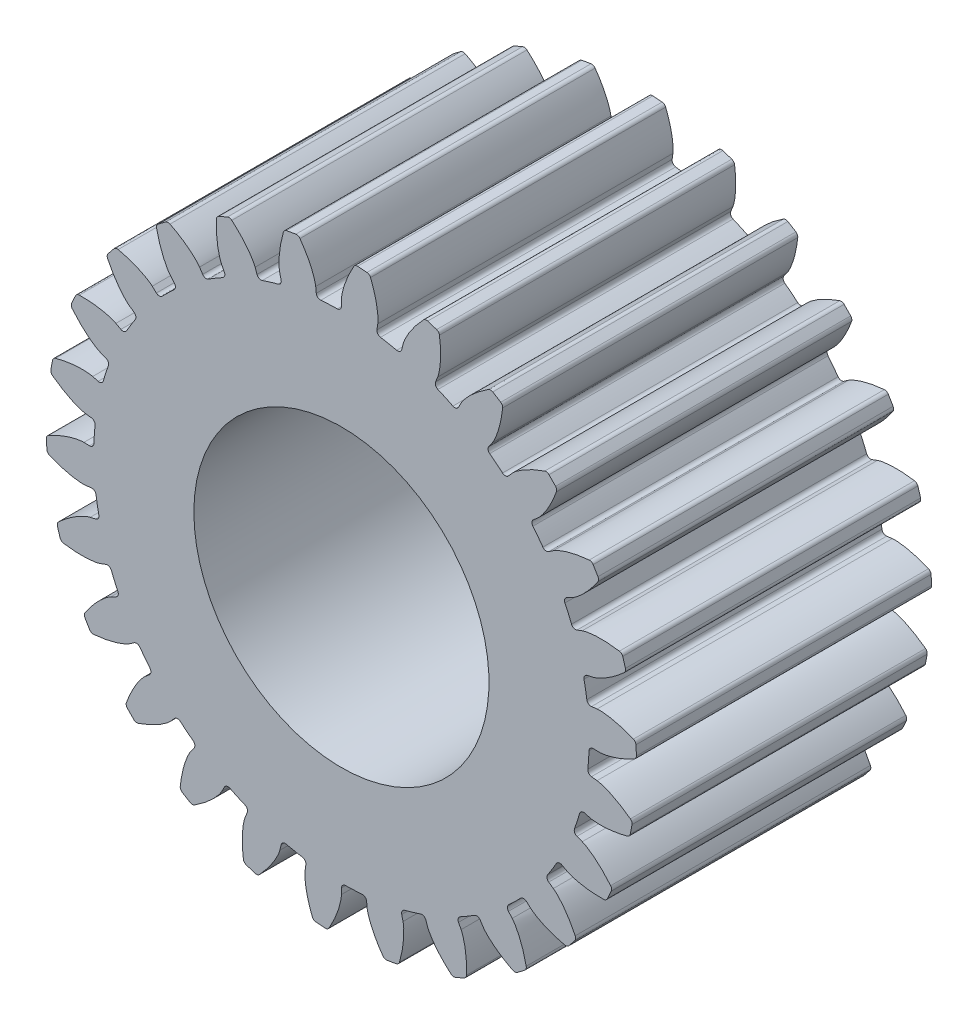
SolidWorks part; units mm, degrees
ref_plane "Front Plane" through (0, 0, 0) normal (0, 0, 1) x (1, 0, 0)
ref_plane "Top Plane" through (0, 0, 0) normal (0, 1, 0) x (1, 0, 0)
ref_plane "Right Plane" through (0, 0, 0) normal (1, 0, 0) x (0, 0, -1)
sketch "Involute Geometry" plane through (0, 0, 0) normal (0, 0, 1) x (1, 0, 0)
  line L0 (0, 12.216) -> (0, 0) construction
  line L1 (0, 0) -> (0.9904, 13.9649) construction
  line L2 (1.724, 12.0937) -> (0, 0) construction
  line L3 (0.175, 12.9988) -> (0, 0) construction
  line L4 (0, 0) -> (1.6612, 12.8934) construction
  circle A1 centre (0, 0) radius 12.216 construction
  circle A2 centre (0, 0) radius 13 construction
  circle A3 centre (0, 0) radius 14 construction
  circle A4 centre (0, 0) radius 11.75 construction
  arc A5 (0.6454, 13.9851) -> (1.3347, 13.9362) centre (0, 0) cw
  arc A6 (0.175, 12.9988) -> (1.6612, 12.8934) centre (0, 0) cw construction
  spline S0 degree 4 poles (0, 12.216) (0, 12.2259) (0.0007, 12.2537) (0.0046, 12.3061) (0.0149, 12.3914) (0.0336, 12.4994) (0.064, 12.638) (0.108, 12.7997) (0.1647, 12.9755) (0.2354, 13.1642) (0.3138, 13.35) (0.3992, 13.5328) (0.4907, 13.7124) (0.6089, 13.9268) (0.7611, 14.1794) (0.9535, 14.4672) (1.1888, 14.7846) (1.4461, 15.0973) (1.7136, 15.3959) (1.9994, 15.6864) (2.287, 15.9594) (2.6008, 16.2305) (2.8982, 16.4744) (3.2472, 16.733) (3.5335, 16.9374) (3.9271, 17.1908) (4.1642, 17.3355) (4.4469, 17.4991) (4.5752, 17.5686) (4.654, 17.6115) knots 0 0 0 0 0 0.005377 0.015084 0.028532 0.04661 0.064855 0.092111 0.119476 0.146842 0.174209 0.201575 0.228941 0.256307 0.307035 0.361767 0.4165 0.471232 0.525964 0.580697 0.635429 0.690161 0.744894 0.799626 0.854358 0.909091 0.954545 1 1 1 1 1 construction
  spline S1 degree 4 poles (0, 12.216) (0, 12.2259) (0.0007, 12.2537) (0.0046, 12.3061) (0.0149, 12.3914) (0.0336, 12.4994) (0.064, 12.638) (0.108, 12.7997) (0.1647, 12.9755) (0.2354, 13.1642) (0.3138, 13.35) (0.3992, 13.5328) (0.4907, 13.7124) (0.6089, 13.9268) (0.7611, 14.1794) (0.9535, 14.4672) (1.1888, 14.7846) (1.4461, 15.0973) (1.7136, 15.3959) (1.9994, 15.6864) (2.287, 15.9594) (2.6008, 16.2305) (2.8982, 16.4744) (3.2472, 16.733) (3.5335, 16.9374) (3.8418, 17.1359) (3.9936, 17.2306) (4.0719, 17.2782) knots 0 0 0 0 0 0.005377 0.015084 0.028532 0.04661 0.064855 0.092111 0.119476 0.146842 0.174209 0.201575 0.228941 0.256307 0.307035 0.361767 0.4165 0.471232 0.525964 0.580697 0.635429 0.690161 0.744894 0.799626 0.854358 0.909091 0.909091 0.909091 0.909091 0.909091
  spline S3 degree 4 poles (1.724, 12.0937) (1.7254, 12.1035) (1.7287, 12.1311) (1.7321, 12.1836) (1.734, 12.2695) (1.7308, 12.379) (1.7202, 12.5206) (1.6995, 12.6869) (1.6681, 12.8689) (1.6248, 13.0657) (1.5734, 13.2607) (1.5147, 13.4537) (1.4495, 13.6444) (1.3626, 13.8734) (1.2477, 14.1449) (1.0977, 14.457) (0.9096, 14.8044) (0.699, 15.1503) (0.4764, 15.4836) (0.2344, 15.8116) (-0.0118, 16.1224) (-0.2842, 16.4351) (-0.5442, 16.7185) (-0.8532, 17.0238) (-1.1078, 17.2666) (-1.4617, 17.573) (-1.676, 17.7497) (-1.9328, 17.9515) (-2.05, 18.0384) (-2.122, 18.092) knots 0 0 0 0 0 0.005377 0.015084 0.028532 0.04661 0.064855 0.092111 0.119476 0.146842 0.174209 0.201575 0.228941 0.256307 0.307035 0.361767 0.4165 0.471232 0.525964 0.580697 0.635429 0.690161 0.744894 0.799626 0.854358 0.909091 0.954545 1 1 1 1 1 construction
  spline S4 degree 4 poles (1.724, 12.0937) (1.7254, 12.1035) (1.7287, 12.1311) (1.7321, 12.1836) (1.734, 12.2695) (1.7308, 12.379) (1.7202, 12.5206) (1.6995, 12.6869) (1.6681, 12.8689) (1.6248, 13.0657) (1.5734, 13.2607) (1.5147, 13.4537) (1.4495, 13.6444) (1.3626, 13.8734) (1.2477, 14.1449) (1.0977, 14.457) (0.9096, 14.8044) (0.699, 15.1503) (0.4764, 15.4836) (0.2344, 15.8116) (-0.0118, 16.1224) (-0.2842, 16.4351) (-0.5442, 16.7185) (-0.8532, 17.0238) (-1.1078, 17.2666) (-1.385, 17.5066) (-1.5219, 17.6217) (-1.5927, 17.6799) knots 0 0 0 0 0 0.005377 0.015084 0.028532 0.04661 0.064855 0.092111 0.119476 0.146842 0.174209 0.201575 0.228941 0.256307 0.307035 0.361767 0.4165 0.471232 0.525964 0.580697 0.635429 0.690161 0.744894 0.799626 0.854358 0.909091 0.909091 0.909091 0.909091 0.909091
  dimension "D5" = 6.57
sketch "Sketch2" plane through (0, 0, 0) normal (0, 0, 1) x (1, 0, 0)
  circle A0 centre (0, 0) radius 11.75 construction
  circle A1 centre (0, 0) radius 11.75
extrude "Boss-Extrude1" add sketch "Sketch2" along normal mid plane 14
sketch "Sketch3" plane through (0, 0, 0) normal (0, 0, 1) x (1, 0, 0)
  line L0 (0, 12.216) -> (0, 0) construction
  line L1 (1.724, 12.0937) -> (0, 0) construction
  line L2 (0, 12.216) -> (0, 11.75)
  line L4 (1.724, 12.0937) -> (1.6583, 11.6324)
  circle A1 centre (0, 0) radius 11.75 construction
  arc A3 (0, 11.75) -> (1.6583, 11.6324) centre (0, 0) cw
  arc A4 (1.3347, 13.9362) -> (0.6454, 13.9851) centre (0, 0) ccw construction
  arc A5 (1.3347, 13.9362) -> (0.6454, 13.9851) centre (0, 0) ccw
  spline S0 degree 4 poles (999.8581, 25.2356) (18.0155, 10.2173) (0.3577, 10.7107) (-0.0848, 11.5636) (0.0149, 12.3914) (0.0336, 12.4994) (0.064, 12.638) (0.108, 12.7997) (0.1647, 12.9755) (0.2354, 13.1642) (0.3138, 13.35) (0.3992, 13.5328) (0.4907, 13.7124) (0.6089, 13.9268) (0.7611, 14.1794) (0.9535, 14.4672) (1.1888, 14.7846) (1.4461, 15.0973) (1.7136, 15.3959) (1.9994, 15.6864) (2.287, 15.9594) (2.6008, 16.2305) (2.8982, 16.4744) (3.2472, 16.733) (4.4419, 17.5861) (8.1221, 19.6216) (-23.9178, -0.2396) (859.2438, 535.5339) knots -0.405932 -0.405932 -0.405932 -0.405932 -0.405932 0.005377 0.015084 0.028532 0.04661 0.064855 0.092111 0.119476 0.146842 0.174209 0.201575 0.228941 0.256307 0.307035 0.361767 0.4165 0.471232 0.525964 0.580697 0.635429 0.690161 0.744894 0.799626 0.854358 1.603617 1.603617 1.603617 1.603617 1.603617 only from (0, 12.216) to (3.8711, 11.595) construction
  spline S1 degree 4 poles (0, 12.216) (0, 12.2259) (0.0007, 12.2537) (0.0046, 12.3061) (0.0149, 12.3914) (0.0336, 12.4994) (0.064, 12.638) (0.108, 12.7997) (0.1647, 12.9755) (0.2354, 13.1642) (0.3138, 13.35) (0.3992, 13.5328) (0.4919, 13.7149) (0.5664, 13.8498) (0.6183, 13.9394) (0.6454, 13.9851) knots 0 0 0 0 0 0.005377 0.015084 0.028532 0.04661 0.064855 0.092111 0.119476 0.146842 0.174209 0.201575 0.228941 0.257808 0.257808 0.257808 0.257808 0.257808
  spline S3 degree 4 poles (-986.2895, 166.0908) (-16.3932, 12.6575) (1.1575, 10.654) (1.7159, 11.4359) (1.734, 12.2695) (1.7308, 12.379) (1.7202, 12.5206) (1.6995, 12.6869) (1.6681, 12.8689) (1.6248, 13.0657) (1.5734, 13.2607) (1.5147, 13.4537) (1.4495, 13.6444) (1.3626, 13.8734) (1.2477, 14.1449) (1.0977, 14.457) (0.9096, 14.8044) (0.699, 15.1503) (0.4764, 15.4836) (0.2344, 15.8116) (-0.0118, 16.1224) (-0.2842, 16.4351) (-0.5442, 16.7185) (-0.8532, 17.0238) (-1.9155, 18.037) (-5.2716, 20.5715) (23.6446, -3.6127) (-775.0652, 651.4371) knots -0.405932 -0.405932 -0.405932 -0.405932 -0.405932 0.005377 0.015084 0.028532 0.04661 0.064855 0.092111 0.119476 0.146842 0.174209 0.201575 0.228941 0.256307 0.307035 0.361767 0.4165 0.471232 0.525964 0.580697 0.635429 0.690161 0.744894 0.799626 0.854358 1.603617 1.603617 1.603617 1.603617 1.603617 only from (1.724, 12.0937) to (-1.5927, 17.6799) construction
  spline S4 degree 4 poles (1.724, 12.0937) (1.7254, 12.1035) (1.7287, 12.1311) (1.7321, 12.1836) (1.734, 12.2695) (1.7308, 12.379) (1.7202, 12.5206) (1.6995, 12.6869) (1.6681, 12.8689) (1.6248, 13.0657) (1.5734, 13.2607) (1.5147, 13.4537) (1.4486, 13.647) (1.3938, 13.7911) (1.3551, 13.8871) (1.3347, 13.9362) knots 0 0 0 0 0 0.005377 0.015084 0.028532 0.04661 0.064855 0.092111 0.119476 0.146842 0.174209 0.201575 0.228941 0.257808 0.257808 0.257808 0.257808 0.257808
extrude "Boss-Extrude2" add sketch "Sketch3" along normal through all and the other way through all
fillet "Fillet2" [suppressed] radius 0.381
pattern_circular "CirPattern1" count 26 over 360 about axis through (0, 0, 7) along (0, 0, -1) of "Boss-Extrude2", "Fillet2"
ref_axis "Axis1" through (0, 0, 7) along (0, 0, -1)
sketch "Sketch4" plane through (0, 0, -7) normal (0, 0, -1) x (-1, 0, 0)
  circle A1 centre (0, 0) radius 7
  dimension "D1" = 14
extrude "Cut-Extrude1" cut sketch "Sketch4" against normal through all
fillet "Fillet3" radius 0.2 104 edges at (-8.6313, 7.9727, 0) (-9.6701, 6.6748, 0) (-10.9864, 4.1666, 0) (-11.3477, 3.0483, 0) (-11.6643, 1.4163, 0) (-11.7475, 0.244, 0) (-11.6643, -1.4163, 0) (-11.4645, -2.5744, 0) (-10.9864, -4.1666, 0) (-10.5153, -5.2432, 0) (-9.6701, -6.6748, 0) (-8.9549, -7.6074, 0) (-7.7917, -8.795, 0) (-6.8742, -9.5293, 0) (-5.4605, -10.4041, 0) (-4.3939, -10.8975, 0) (-2.812, -11.4086, 0) (-1.6583, -11.6324, 0) (0, -11.75, 0) (1.1737, -11.6912, 0) (2.812, -11.4086, 0) (3.9375, -11.0706, 0) (5.4605, -10.4041, 0) (6.4725, -9.8066, 0) (7.7917, -8.795, 0) (8.6313, -7.9727, 0) (9.6701, -6.6748, 0) (10.2885, -5.6754, 0) (10.9864, -4.1666, 0) (11.3477, -3.0483, 0) (11.6643, -1.4163, 0) (11.7475, -0.244, 0) (11.6643, 1.4163, 0) (11.4645, 2.5744, 0) (10.9864, 4.1666, 0) (10.5153, 5.2432, 0) (9.6701, 6.6748, 0) (8.9549, 7.6074, 0) (7.7917, 8.795, 0) (6.8742, 9.5293, 0) (5.4605, 10.4041, 0) (4.3939, 10.8975, 0) (2.812, 11.4086, 0) (1.6583, 11.6324, 0) (0, 11.75, 0) (-10.2885, 5.6754, 0) (-1.1737, 11.6912, 0) (-2.812, 11.4086, 0) (-3.9375, 11.0706, 0) (-5.4605, 10.4041, 0) (-6.4725, 9.8066, 0) (-7.7917, 8.795, 0) (1.3347, 13.9362, 0) (3.9735, 13.4243, 0) (4.6311, 13.2119, 0) (7.0707, 12.0833, 0) (7.6583, 11.7197, 0) (9.757, 10.04, 0) (10.2405, 9.5463, 0) (11.8762, 7.4133, 0) (12.2275, 6.8182, 0) (13.3052, 4.3557, 0) (13.5039, 3.6939, 0) (13.9609, 1.045, 0) (13.9955, 0.3548, 0) (13.8053, -2.3265, 0) (13.6737, -3.0048, 0) (12.8474, -5.5627, 0) (12.5573, -6.1898, 0) (11.1429, -8.4756, 0) (10.7111, -9.0151, 0) (8.7907, -10.896, 0) (8.2424, -11.3165, 0) (5.9277, -12.6832, 0) (5.2947, -12.9602, 0) (2.7202, -13.7332, 0) (2.0392, -13.8507, 0) (-0.6454, -13.9851, 0) (-1.3347, -13.9362, 0) (-3.9735, -13.4243, 0) (-4.6311, -13.2119, 0) (-7.0707, -12.0833, 0) (-7.6583, -11.7197, 0) (-9.757, -10.04, 0) (-10.2405, -9.5463, 0) (-11.8762, -7.4133, 0) (-12.2275, -6.8182, 0) (-13.3052, -4.3557, 0) (-13.5039, -3.6939, 0) (-13.9609, -1.045, 0) (-13.9955, -0.3548, 0) (-13.8053, 2.3265, 0) (-13.6737, 3.0048, 0) (-12.8474, 5.5627, 0) (-12.5573, 6.1898, 0) (-11.1429, 8.4756, 0) (-10.7111, 9.0151, 0) (-8.7907, 10.896, 0) (-8.2424, 11.3165, 0) (-5.9277, 12.6832, 0) (-5.2947, 12.9602, 0) (-2.7202, 13.7332, 0) (-2.0392, 13.8507, 0) (0.6454, 13.9851, 0)
equation "\"N\"= 26'Number of Teeth"
equation "\"m\"= 1mm'Diametral Pitch"
equation "\"phi\"= 20deg'Pressure Angle"
equation "\"a\"= \"m\"'Addendum"
equation "\"b\"= 1.25 * \"m\"'Dedendum"
equation "\"Dp\"= \"N\" * \"m\"'Pitch diameter"
equation "\"Db\"= \"Dp\" * cos ( \"phi\" )'Base diameter"
equation "\"D1@Involute Geometry\" = \"Db\""
equation "\"D2@Involute Geometry\" = \"Dp\""
equation "\"D3@Involute Geometry\" = \"Dp\" + 2 * \"a\""
equation "\"D4@Involute Geometry\" = \"Dp\" - 2 * \"b\""
equation "\"D1@CirPattern1\"=\"N\""
equation "\"D5@Involute Geometry\"=180/\"N\"-\"j_th\"/2"
equation "\"D1@Boss-Extrude1\"=14*\"m\""
equation "\"j_th\"= ( 360deg ) * ( 0.16mm ) / ( pi * \"Dp\" )'Angular backlash"
equation "\"alpha\"= sqr ( \"Dp\" ^ 2 - \"Db\" ^ 2 ) / \"Db\" * 180 / pi - \"phi\""
equation "\"beta\"= ( ( 360deg / \"N\" ) / 4 - \"alpha\" )"
